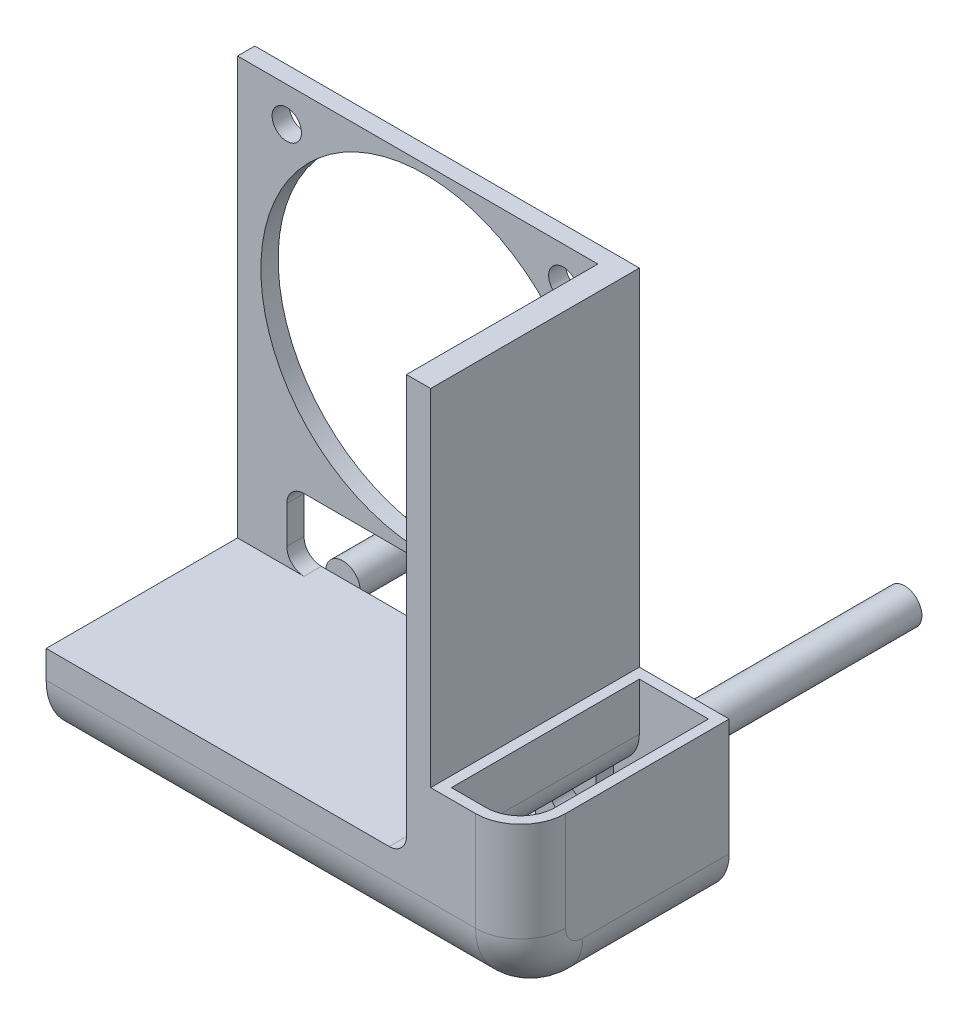
SolidWorks part; units mm, degrees
ref_plane "Front" through (0, 0, 0) normal (0, 0, 1) x (1, 0, 0)
ref_plane "Top" through (0, 0, 0) normal (0, 1, 0) x (1, 0, 0)
ref_plane "Right" through (0, 0, 0) normal (1, 0, 0) x (0, 0, -1)
sketch "Sketch1" plane through (0, 0, 0) normal (0, 0, 1) x (1, 0, 0)
  line L1 (0, 0) -> (40, 0)
  line L2 (0, 0) -> (0, 40)
  line L3 (0, 40) -> (40, 40)
  line L4 (40, 0) -> (40, 40)
  line L5 (20, 40) -> (20, 0) construction
  line L6 (0, 20) -> (40, 20) construction
  point P204 (20, 20)
  dimension "D1" = 40
  dimension "D2" = 40
extrude "Boss-Extrude1" add sketch "Sketch1" along normal blind 2 contours L4 L3 L2 L1 | L4 | L4 region at (20, 20, 0)
hole_wizard "M3 Clearance Hole1" positions "Sketch2" profile "Sketch3" hole size "M3" standard "ANSI Metric" end condition through all
sketch "Sketch2" plane through (0, 0, 2) normal (0, 0, 1) x (1, 0, 0)
  line L4 (4, 36) -> (36, 4) construction
  line L5 (36, 4) -> (36, 36) construction
  line L6 (36, 36) -> (4, 4) construction
  line L8 (0, 20) -> (20, 20) construction
  line L9 (0, 0) -> (0, 40) construction
  line L11 (20, 20) -> (20, 40) construction
  line L12 (0, 40) -> (40, 40) construction
  point P0 (4, 36)
  point P2 (36, 4)
  point P12 (4, 4)
  point P14 (36, 36)
  dimension "D1" = 32
  dimension "D2" = 32
sketch "Sketch3" plane through (4, 36, 2) normal (1, 0, 0) x (0, -1, 0)
  line L0 (0, 0) -> (0, 2)
  line L1 (0, 2) -> (1.7, 2)
  line L2 (1.7, 2) -> (1.7, 0)
  line L5 (1.7, 0) -> (0, 0)
  line L11 (0, -6.35) -> (0, 107.95) construction
  dimension "Thru Hole Dia." = 3.4
  dimension "Thru Hole Depth" = 2
sketch "Sketch10" plane through (0, 0, 2) normal (0, 0, 1) x (1, 0, 0)
  line L1 (0, 0) -> (40, 0)
  line L2 (0, 0) -> (0, -8.3)
  line L3 (0, -8.3) -> (40, -8.3)
  line L4 (40, 0) -> (40, -8.3)
  dimension "D1" = 8.3
extrude "Boss-Extrude7" add sketch "Sketch10" against normal blind 2
sketch "Sketch20" plane through (0, 0, 0) normal (0, 0, -1) x (-1, 0, 0)
  line L0 (-37.5, -14.5) -> (-2.5, -14.5) construction
  line L1 (-20, -14.5) -> (-20, -8.3) construction
  line L2 (0, -8.3) -> (-40, -8.3) construction
  circle A0 centre (-37.5, -14.5) radius 2
  circle A1 centre (-2.5, -14.5) radius 2
  dimension "D3" = 4
  dimension "D1" = 35
  dimension "D2" = 14.5
extrude "Boss-Extrude10" add sketch "Sketch20" along normal blind 30 from offset 6 separate body
sketch "Sketch21" plane through (0, 0, 0) normal (0, 1, 0) x (1, 0, 0)
  line L0 (40, -2) -> (40, 0) construction
  line L1 (44, -22.95) -> (52, -22.95)
  line L2 (44, -22.95) -> (44, -1.2)
  line L3 (44, -1.2) -> (52, -1.2)
  line L4 (52, -22.95) -> (52, -1.2)
  line L8 (0, 0) -> (40, 0) construction
  dimension "D1" = 21.75
  dimension "D2" = 8
  dimension "D3" = 4
  dimension "D4" = 1.2
ref_plane "Plane1" through (0, 0, 22.95) normal (0, 0, -1) x (-1, 0, 0)
sketch "Sketch22" plane through (0, 0, 22.95) normal (0, 0, -1) x (-1, 0, 0)
  line L7 (-44, 0) -> (-52, 0)
  line L8 (-44, 0) -> (-52, 0) construction
  line L10 (-52, 0) -> (-52, -17.5)
  line L11 (-52, -17.5) -> (0.5, -17.5)
  line L12 (0.5, -17.5) -> (0.5, -9.5)
  line L13 (0.5, -9.5) -> (-44, -9.5)
  line L14 (-44, -9.5) -> (-44, 0)
  circle A6 centre (-37.5, -14.5) radius 2 construction
  circle A7 centre (-2.5, -14.5) radius 2 construction
  dimension "D2" = 3
  dimension "D1" = 3
  dimension "D3" = 8
extrude "Boss-Extrude11" add sketch "Sketch22" along normal blind 21.75 separate body
fillet "Fillet4" radius 6 1 edges at (25.75, -17.5, 22.95)
chamfer "Chamfer1" [suppressed] distance 7.5 angle 45
fillet "Fillet1" radius 4 4 edges at (52, -17.5, 9.075) (44, -9.5, 12.075) (52, -5.75, 22.95) (52, -15.7426, 21.1926)
shell "Shell1" thickness 1.2 removed face at (48.1657, 0, 13.6157) outward yes
sketch "Sketch25" plane through (0, 0, 0) normal (0, 0, -1) x (-1, 0, 0)
  line L0 (-40, -8.3) -> (-40, 40) construction
  line L1 (-42.8, -8.3) -> (-40, -8.3)
  line L2 (-42.8, -8.3) -> (-42.8, 40)
  line L3 (-42.8, 40) -> (-40, 40)
  line L4 (-40, -8.3) -> (-40, 40)
  line L6 (0, 40) -> (-40, 40) construction
extrude "Boss-Extrude14" add sketch "Sketch25" against normal up to surface (24.15 mm away) up to face at (31.2543, -6.5257, 24.15)
sketch "Sketch26" plane through (0, 0, 2) normal (0, 0, 1) x (1, 0, 0)
  line L0 (0, -8.3) -> (0, 40) construction
  line L1 (40, -8.3) -> (4, -8.3)
  line L2 (40, -8.3) -> (40, 0)
  line L3 (40, 0) -> (4, 0)
  line L4 (4, -8.3) -> (4, 0)
  dimension "D1" = 4
extrude "Cut-Extrude5" cut sketch "Sketch26" against normal through all
sketch "Sketch27" plane through (0, 0, 2) normal (0, 0, 1) x (1, 0, 0)
  line L0 (4, 36) -> (36, 4) construction
  circle A0 centre (20, 20) radius 19
  dimension "D1" = 38
extrude "Cut-Extrude6" cut sketch "Sketch27" against normal through all
fillet "Fillet2" radius 2 3 edges at (4, 0, 1) (4, -8.3, 1) (40, 0, 1)
fillet "Fillet3" radius 2 1 edges at (40, -8.3, 12.075)
sketch "Sketch29" plane through (0, 0, 2) normal (0, 0, 1) x (1, 0, 0)
  line L1 (0, 40) -> (-1.7, 40)
  line L2 (0, 40) -> (0, -8.3)
  line L3 (0, -8.3) -> (-1.7, -8.3)
  line L4 (-1.7, 40) -> (-1.7, -8.3)
extrude "Boss-Extrude15" add sketch "Sketch29" against normal up to surface (2 mm away) up to face at (39, 20, 0)
other "DeleteFace1" face at (5.7, 4, 0) and patch yes
sketch "Sketch32" plane through (0, 0, 1.2) normal (0, 0, 1) x (1, 0, 0)
  line L0 (-0.5, -9.5) -> (40, -9.5) construction
  line L1 (6, -9.5) -> (-1, -9.5)
  line L2 (6, -9.5) -> (6, -17.5)
  line L3 (6, -17.5) -> (-1, -17.5)
  line L4 (-1, -9.5) -> (-1, -17.5)
  line L5 (2.5, -17.5) -> (2.5, -9.5) construction
  line L6 (6, -13.5) -> (-1, -13.5) construction
  line L7 (48, -17.5) -> (-0.5, -17.5) construction
  line L8 (2.5, -13.5) -> (37.5, -13.5) construction
  line L9 (34, -9.5) -> (41, -9.5)
  line L10 (34, -9.5) -> (34, -17.5)
  line L11 (34, -17.5) -> (41, -17.5)
  line L12 (41, -9.5) -> (41, -17.5)
  line L13 (37.5, -17.5) -> (37.5, -9.5) construction
  line L14 (34, -13.5) -> (41, -13.5) construction
  line L15 (20, -13.5) -> (20, 20) construction
  point P124 (37.5, -13.5)
  point P148 (2.5, -13.5)
  dimension "D1" = 35
  dimension "D2" = 7
extrude "Boss-Extrude16" add sketch "Sketch32" along normal blind 2
hole_wizard "Ø3.5 (3.5) Diameter Hole1" positions "Sketch30" profile "Sketch31" hole size "Ø3.5" standard "ANSI Metric" end condition up to next
sketch "Sketch30" plane through (0, 0, 0) normal (0, 0, -1) x (-1, 0, 0)
  line L0 (-20, 20) -> (-20, -14.5) construction
  line L3 (-37.5, -14.5) -> (-2.5, -14.5) construction
  point P0 (-37.5, -14.5)
  point P2 (-2.5, -14.5)
  dimension "D1" = 35
  dimension "D2" = 34.5
sketch "Sketch31" plane through (37.5, -14.5, 0) normal (1, 0, 0) x (0, 1, 0)
  line L0 (0, 0) -> (0, 3.201)
  line L1 (0, 3.201) -> (1.75, 3.201)
  line L2 (1.75, 3.201) -> (1.75, 0)
  line L5 (1.75, 0) -> (0, 0)
  line L11 (0, -6.35) -> (0, 107.95) construction
  dimension "Thru Hole Dia." = 3.5
  dimension "Thru Hole Depth" = 3.201
